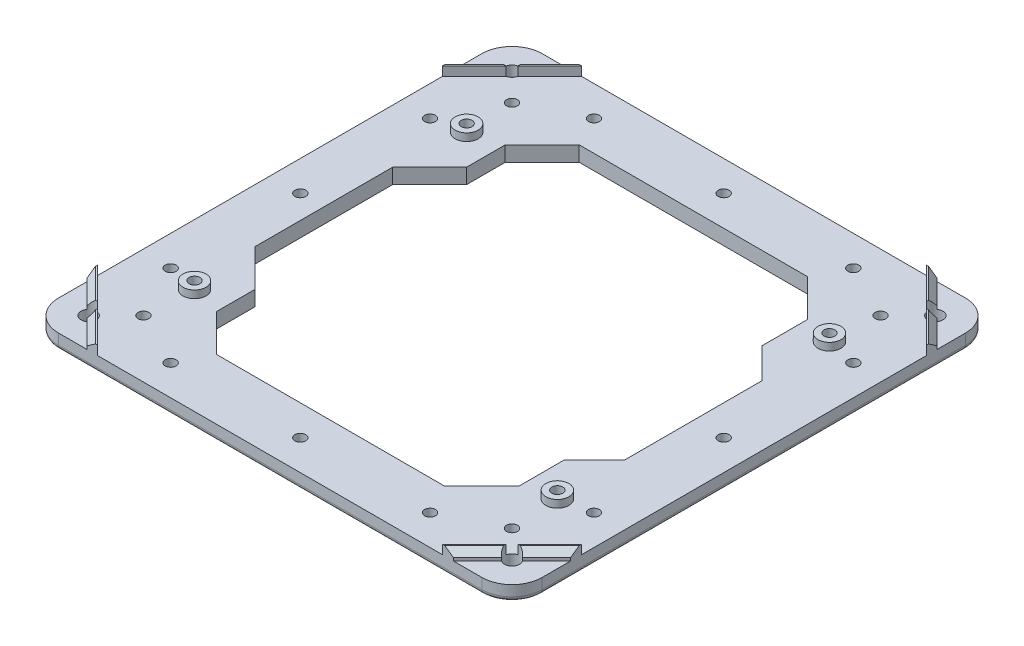
SolidWorks part; units mm, degrees
ref_plane "Front Plane" through (0, 0, 0) normal (0, 0, 1) x (1, 0, 0)
ref_plane "Top Plane" through (0, 0, 0) normal (0, 1, 0) x (1, 0, 0)
ref_plane "Right Plane" through (0, 0, 0) normal (1, 0, 0) x (0, 0, -1)
sketch "Sketch1" plane through (0, 0, 0) normal (0, 1, 0) x (1, 0, 0)
  line L1 (0, 0) -> (203.2, 0)
  line L2 (0, 0) -> (0, 203.2)
  line L3 (0, 203.2) -> (203.2, 203.2)
  line L4 (203.2, 0) -> (203.2, 203.2)
  dimension "D1" = 203.2
  dimension "D2" = 203.2
extrude "Boss-Extrude1" add sketch "Sketch1" along normal blind 6.35
fillet "Fillet1" radius 12.7 4 edges at (0, 3.175, -203.2) (0, 3.175, 0) (203.2, 3.175, 0) (203.2, 3.175, -203.2)
sketch "Sketch2" plane through (0, 0, 0) normal (0, -1, 0) x (1, 0, 0)
  circle A0 centre (12.7, -12.7) radius 3.175
  circle A1 centre (190.5, -12.7) radius 3.175
  circle A2 centre (190.5, -190.5) radius 3.175
  circle A3 centre (12.7, -190.5) radius 3.175
  arc A4 (190.5, -203.2) -> (203.2, -190.5) centre (190.5, -190.5) ccw construction
  arc A5 (12.7, 0) -> (0, -12.7) centre (12.7, -12.7) ccw construction
  arc A6 (12.7, 0) -> (0, -12.7) centre (12.7, -12.7) ccw construction
  dimension "D1" = 6.35
  dimension "D2" = 9.525
extrude "Cut-Extrude1" cut sketch "Sketch2" against normal through all
fillet "Fillet2" radius 1.905 12 edges at (3.7197, 0, -3.7197) (101.6, 0, 0) (199.4803, 0, -3.7197) (203.2, 0, -101.6) (199.4803, 0, -199.4803) (101.6, 0, -203.2) (3.7197, 0, -199.4803) (0, 0, -101.6) (12.7, 0, -15.875) (190.5, 0, -15.875) (190.5, 0, -193.675) (12.7, 0, -193.675)
sketch "Sketch3" plane through (0, 6.35, 0) normal (0, 1, 0) x (1, 0, 0)
  line L0 (3.7197, 3.7197) -> (24.1978, 24.1978) construction
  line L1 (24.1978, 24.1978) -> (0, 24.1978) construction
  line L2 (0, 190.5) -> (0, 12.7) construction
  line L3 (24.1978, 24.1978) -> (24.1978, 0) construction
  line L4 (12.7, 0) -> (190.5, 0) construction
  line L5 (3.7197, 199.4803) -> (24.1978, 179.0022) construction
  line L6 (0, 179.0022) -> (24.1978, 179.0022) construction
  line L7 (24.1978, 179.0022) -> (24.1978, 203.2) construction
  line L8 (190.5, 203.2) -> (12.7, 203.2) construction
  line L9 (199.4803, 3.7197) -> (179.0022, 24.1978) construction
  line L10 (179.0022, 24.1978) -> (179.0022, 0) construction
  line L12 (179.0022, 24.1978) -> (203.2, 24.1978) construction
  line L13 (203.2, 12.7) -> (203.2, 190.5) construction
  line L14 (199.4803, 199.4803) -> (179.0022, 179.0022) construction
  line L15 (179.0022, 179.0022) -> (203.2, 179.0022) construction
  line L16 (179.0022, 179.0022) -> (179.0022, 203.2) construction
  arc A0 (0, 12.7) -> (12.7, 0) centre (12.7, 12.7) ccw construction
  circle A1 centre (24.1978, 24.1978) radius 2.286
  arc A2 (190.5, 0) -> (203.2, 12.7) centre (190.5, 12.7) ccw construction
  arc A3 (203.2, 190.5) -> (190.5, 203.2) centre (190.5, 190.5) ccw construction
  arc A10 (12.7, 203.2) -> (0, 190.5) centre (12.7, 190.5) ccw construction
  circle A13 centre (179.0022, 179.0022) radius 2.286
  circle A14 centre (179.0022, 24.1978) radius 2.286
  circle A15 centre (24.1978, 179.0022) radius 2.286
  point P20 (101.6, 101.6)
  dimension "D2" = 4.572
  dimension "D1" = 28.9603
extrude "Cut-Extrude2" cut sketch "Sketch3" against normal through all
sketch "Sketch4" plane through (0, 6.35, 0) normal (0, 1, 0) x (1, 0, 0)
  line L0 (0, 190.5) -> (0, 12.7) construction
  line L1 (203.2, 12.7) -> (203.2, 190.5) construction
  line L2 (12.7, 0) -> (190.5, 0) construction
  line L3 (3.7197, 3.7197) -> (199.4803, 199.4803) construction
  circle A0 centre (47.117, 12.7) radius 2.286
  circle A1 centre (156.083, 12.7) radius 2.286
  arc A2 (0, 12.7) -> (12.7, 0) centre (12.7, 12.7) ccw construction
  arc A3 (203.2, 190.5) -> (190.5, 203.2) centre (190.5, 190.5) ccw construction
  circle A4 centre (12.7, 156.083) radius 2.286
  circle A5 centre (12.7, 47.117) radius 2.286
  circle A6 centre (156.083, 190.5) radius 2.286
  circle A7 centre (47.117, 190.5) radius 2.286
  circle A8 centre (190.5, 47.117) radius 2.286
  circle A9 centre (190.5, 156.083) radius 2.286
  circle A10 centre (101.6, 12.7) radius 2.286
  circle A11 centre (12.7, 101.6) radius 2.286
  circle A12 centre (101.6, 190.5) radius 2.286
  circle A13 centre (190.5, 101.6) radius 2.286
  point P18 (101.6, 101.6)
  dimension "D4" = 4.572
  dimension "D1" = 47.117
  dimension "D2" = 47.117
  dimension "D3" = 12.7
  dimension "D6" = 104.267
  dimension "D7" = 34.417
  dimension "D8" = 54.483
  dimension "D5" = 4
extrude "Cut-Extrude3" cut sketch "Sketch4" against normal through all
sketch "Sketch5" plane through (0, 6.35, 0) normal (0, 1, 0) x (1, 0, 0)
  line L0 (0, 190.5) -> (0, 12.7) construction
  line L1 (203.2, 12.7) -> (203.2, 190.5) construction
  line L2 (12.7, 0) -> (190.5, 0) construction
  line L3 (190.5, 203.2) -> (12.7, 203.2) construction
  circle A0 centre (25.4, 158.75) radius 2.286
  circle A1 centre (177.8, 158.75) radius 2.286
  circle A2 centre (177.8, 44.45) radius 2.286
  circle A3 centre (25.4, 44.45) radius 2.286
  circle A4 centre (25.4, 158.75) radius 4.826
  circle A5 centre (177.8, 158.75) radius 4.826
  circle A6 centre (177.8, 44.45) radius 4.826
  circle A7 centre (25.4, 44.45) radius 4.826
  dimension "D1" = 2.54
  dimension "D2" = 4.572
  dimension "D3" = 25.4
  dimension "D4" = 25.4
  dimension "D5" = 44.45
  dimension "D6" = 44.45
extrude "Boss-Extrude2" add sketch "Sketch5" along normal blind 3.175
sketch "Sketch6" plane through (0, 6.35, 0) normal (0, 1, 0) x (1, 0, 0)
  line L0 (203.2, 29.1287) -> (189.8864, 15.8151)
  line L1 (203.2, 12.7) -> (203.2, 190.5) construction
  line L2 (12.7, 0) -> (190.5, 0) construction
  line L3 (203.2, 29.1287) -> (203.2, 24.6386)
  line L4 (203.2, 24.6386) -> (193.0933, 14.5318)
  line L5 (178.5614, 0) -> (174.0713, 0)
  line L6 (187.3849, 13.3136) -> (174.0713, 0)
  line L7 (188.6682, 10.1067) -> (178.5614, 0)
  line L8 (3.7197, 3.7197) -> (199.4803, 199.4803) construction
  line L9 (13.3136, 15.8151) -> (0, 29.1287)
  line L10 (0, 24.6386) -> (0, 29.1287)
  line L11 (10.1067, 14.5318) -> (0, 24.6386)
  line L12 (24.6386, 0) -> (14.5318, 10.1067)
  line L13 (29.1287, 0) -> (15.8151, 13.3136)
  line L14 (29.1287, 0) -> (24.6386, 0)
  line L15 (15.8151, 189.8864) -> (29.1287, 203.2)
  line L16 (24.6386, 203.2) -> (29.1287, 203.2)
  line L17 (14.5318, 193.0933) -> (24.6386, 203.2)
  line L18 (0, 178.5614) -> (10.1067, 188.6682)
  line L19 (0, 174.0713) -> (13.3136, 187.3849)
  line L20 (0, 174.0713) -> (0, 178.5614)
  line L21 (189.8864, 187.3849) -> (203.2, 174.0713)
  line L22 (203.2, 178.5614) -> (203.2, 174.0713)
  line L23 (193.0933, 188.6682) -> (203.2, 178.5614)
  line L24 (178.5614, 203.2) -> (188.6682, 193.0933)
  line L25 (174.0713, 203.2) -> (187.3849, 189.8864)
  line L26 (174.0713, 203.2) -> (178.5614, 203.2)
  arc A0 (187.3849, 13.3136) -> (188.6682, 10.1067) centre (190.5, 12.7) ccw
  arc A1 (193.0933, 14.5318) -> (189.8864, 15.8151) centre (190.5, 12.7) ccw
  arc A2 (0, 12.7) -> (12.7, 0) centre (12.7, 12.7) ccw construction
  arc A3 (203.2, 190.5) -> (190.5, 203.2) centre (190.5, 190.5) ccw construction
  arc A4 (13.3136, 15.8151) -> (10.1067, 14.5318) centre (12.7, 12.7) ccw
  arc A5 (14.5318, 10.1067) -> (15.8151, 13.3136) centre (12.7, 12.7) ccw
  arc A6 (15.8151, 189.8864) -> (14.5318, 193.0933) centre (12.7, 190.5) ccw
  arc A7 (10.1067, 188.6682) -> (13.3136, 187.3849) centre (12.7, 190.5) ccw
  arc A8 (189.8864, 187.3849) -> (193.0933, 188.6682) centre (190.5, 190.5) ccw
  arc A9 (188.6682, 193.0933) -> (187.3849, 189.8864) centre (190.5, 190.5) ccw
  point P22 (101.6, 101.6)
  dimension "D4" = 6.35
  dimension "D1" = 29.1287
  dimension "D2" = 29.1287
  dimension "D3" = 3.175
  dimension "D6" = 177.8
  dimension "D5" = 4
extrude "Boss-Extrude3" add sketch "Sketch6" along normal blind 3.81
chamfer "Chamfer1" distance 2.54 angle 45 8 edges at (198.1466, 10.16, -19.5852) (183.6148, 10.16, -5.0534) (198.1466, 10.16, -183.6148) (183.6148, 10.16, -198.1466) (19.5852, 10.16, -198.1466) (5.0534, 10.16, -183.6148) (19.5852, 10.16, -5.0534) (5.0534, 10.16, -19.5852)
sketch "Sketch7" plane through (0, 6.35, 0) normal (0, 1, 0) x (1, 0, 0)
  line L0 (38.1, 57.15) -> (38.1, 25.4)
  line L1 (38.1, 177.8) -> (165.1, 177.8)
  line L2 (38.1, 177.8) -> (38.1, 146.05)
  line L3 (38.1, 25.4) -> (165.1, 25.4)
  line L4 (165.1, 177.8) -> (165.1, 146.05)
  line L5 (38.1, 57.15) -> (22.5685, 57.15)
  line L7 (38.1, 146.05) -> (22.5685, 146.05)
  line L8 (22.5685, 57.15) -> (22.5685, 146.05)
  line L9 (165.1, 57.15) -> (177.8, 57.15)
  line L11 (165.1, 146.05) -> (177.8, 146.05)
  line L12 (177.8, 57.15) -> (177.8, 146.05)
  line L13 (165.1, 57.15) -> (165.1, 25.4)
  circle A0 centre (47.117, 190.5) radius 2.286 construction
  circle A1 centre (101.6, 12.7) radius 2.286 construction
  circle A2 centre (177.8, 44.45) radius 4.826 construction
  circle A3 centre (25.4, 44.45) radius 2.286 construction
  circle A4 centre (190.5, 156.083) radius 2.286 construction
  circle A5 centre (177.8, 158.75) radius 4.826 construction
  circle A6 centre (25.4, 44.45) radius 4.826 construction
  dimension "D6" = 12.7
  dimension "D8" = 12.7
  dimension "D1" = 12.7
  dimension "D2" = 12.7
  dimension "D3" = 12.7
  dimension "D4" = 12.7
  dimension "D5" = 12.7
  dimension "D7" = 12.7
extrude "Cut-Extrude4" cut sketch "Sketch7" against normal through all
chamfer "Chamfer2" distance 15.5448 angle 45 8 edges at (22.5685, 3.175, -57.15) (38.1, 3.175, -25.4) (165.1, 3.175, -25.4) (177.8, 3.175, -57.15) (177.8, 3.175, -146.05) (165.1, 3.175, -177.8) (38.1, 3.175, -177.8) (22.5685, 3.175, -146.05)
